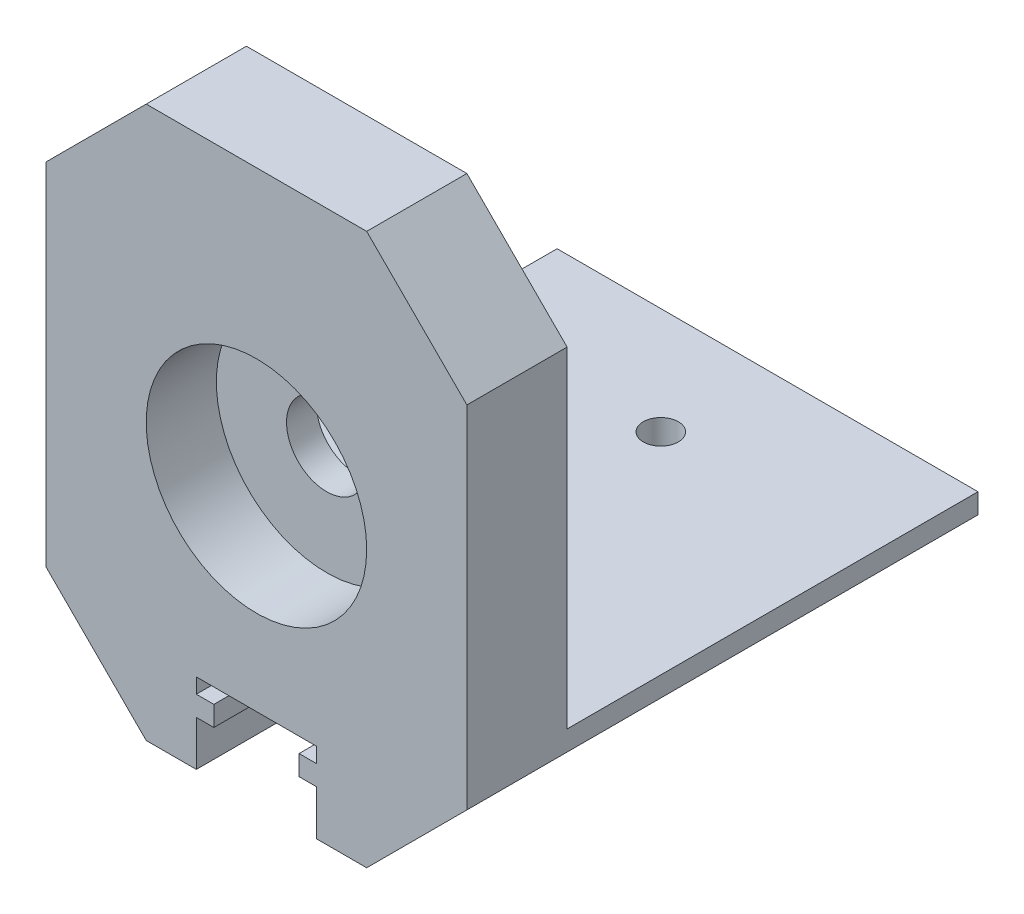
SolidWorks part; units mm, degrees
material "PLA"
ref_plane "Piano frontale" through (0, 0, 0) normal (0, 0, 1) x (1, 0, 0)
ref_plane "Piano superiore" through (0, 0, 0) normal (0, 1, 0) x (1, 0, 0)
ref_plane "Piano destro" through (0, 0, 0) normal (1, 0, 0) x (0, 0, -1)
sketch "Schizzo1" plane through (0, 0, 0) normal (0, 0, 1) x (1, 0, 0)
  line L0 (6, -23) -> (6, -27.5)
  line L1 (-21, -27.5) -> (-6, -27.5)
  line L2 (-21, -27.5) -> (-21, 27.5)
  line L3 (-21, 27.5) -> (21, 27.5)
  line L4 (21, -27.5) -> (21, 27.5)
  line L5 (-21, -27.5) -> (21, 27.5) construction
  line L6 (-21, 27.5) -> (21, -27.5) construction
  line L7 (6, -19.5) -> (6, -21)
  line L8 (6, -19.5) -> (-6, -19.5)
  line L9 (-6, -19.5) -> (-6, -21)
  line L11 (6, -19.5) -> (-6, -27.5) construction
  line L12 (-6, -19.5) -> (6, -27.5) construction
  line L13 (6, -21) -> (4.25, -21)
  line L14 (4.25, -21) -> (4.25, -23)
  line L15 (6, -23) -> (4.25, -23)
  line L16 (-6, -21) -> (-4.25, -21)
  line L17 (-4.25, -21) -> (-4.25, -23)
  line L18 (-6, -23) -> (-4.25, -23)
  line L19 (-6, -23) -> (-6, -27.5)
  line L20 (6, -27.5) -> (21, -27.5)
  point P0 (0, 0)
  point P6 (0, -23.5)
  point P21 (0, 0)
  dimension "D1" = 42
  dimension "D2" = 55
  dimension "D3" = 12
  dimension "D4" = 8
  dimension "D5" = 2
  dimension "D6" = 2
  dimension "D7" = 1.5
  dimension "D8" = 1.5
  dimension "D9" = 8.5
  dimension "D10" = 4.25
extrude "Estrusione-Estrusione1" add sketch "Schizzo1" along normal blind 10
sketch "Schizzo2" plane through (0, 0, 10) normal (0, 0, 1) x (1, 0, 0)
  circle A0 centre (0, 0) radius 11
  point P4 (0, 0)
  point P5 (0, 0)
  dimension "D1" = 22
extrude "Taglio-Estrusione1" cut sketch "Schizzo2" against normal blind 7
sketch "Schizzo3" plane through (0, 0, 3) normal (0, 0, 1) x (1, 0, 0)
  circle A0 centre (0, 0) radius 4
  dimension "D1" = 8
extrude "Taglio-Estrusione2" cut sketch "Schizzo3" against normal through all
sketch "Schizzo4" plane through (0, 0, 0) normal (0, 0, -1) x (-1, 0, 0)
  line L0 (-21, -27.5) -> (-6, -27.5)
  line L1 (-6, -27.5) -> (-21, -27.5) construction
  line L2 (-6, -27.5) -> (-6, -23)
  line L3 (-6, -23) -> (-4.25, -23)
  line L4 (-4.25, -23) -> (-4.25, -21)
  line L5 (-4.25, -21) -> (-6, -21)
  line L8 (-21, -27.5) -> (-21, -15.5)
  line L9 (-21, -27.5) -> (-21, 27.5) construction
  line L11 (-21, -15.5) -> (21, -15.5)
  line L12 (0, -15.5) -> (0, 0) construction
  line L13 (-6, -21) -> (-6, -19.5)
  line L14 (-6, -19.5) -> (6, -19.5)
  line L15 (6, -19.5) -> (-6, -19.5) construction
  line L16 (6, -21) -> (6, -19.5)
  line L17 (21, -27.5) -> (21, -15.5)
  line L18 (4.25, -21) -> (6, -21)
  line L19 (4.25, -23) -> (4.25, -21)
  line L20 (6, -23) -> (4.25, -23)
  line L21 (6, -27.5) -> (6, -23)
  line L22 (21, -27.5) -> (6, -27.5)
  point P25 (0, -19.5)
  dimension "D1" = 5.5
extrude "Estrusione-Estrusione2" add sketch "Schizzo4" along normal blind 41
chamfer "Smusso1" distance 10 angle 45 4 edges at (-21, 27.5, 5) (21, 27.5, 5) (-21, -27.5, -15.5) (21, -27.5, -15.5)
sketch "Schizzo5" plane through (0, -15.5, 0) normal (0, 1, 0) x (1, 0, 0)
  line L0 (0, 41) -> (0, 0) construction
  line L1 (-21, 41) -> (21, 41) construction
  circle A0 centre (0, 30.35) radius 1.75
  circle A1 centre (0, 5.35) radius 1.75
  dimension "D1" = 3.5
  dimension "D3" = 3.5
  dimension "D2" = 10.65
  dimension "D4" = 25
extrude "Taglio-Estrusione3" cut sketch "Schizzo5" against normal through all
